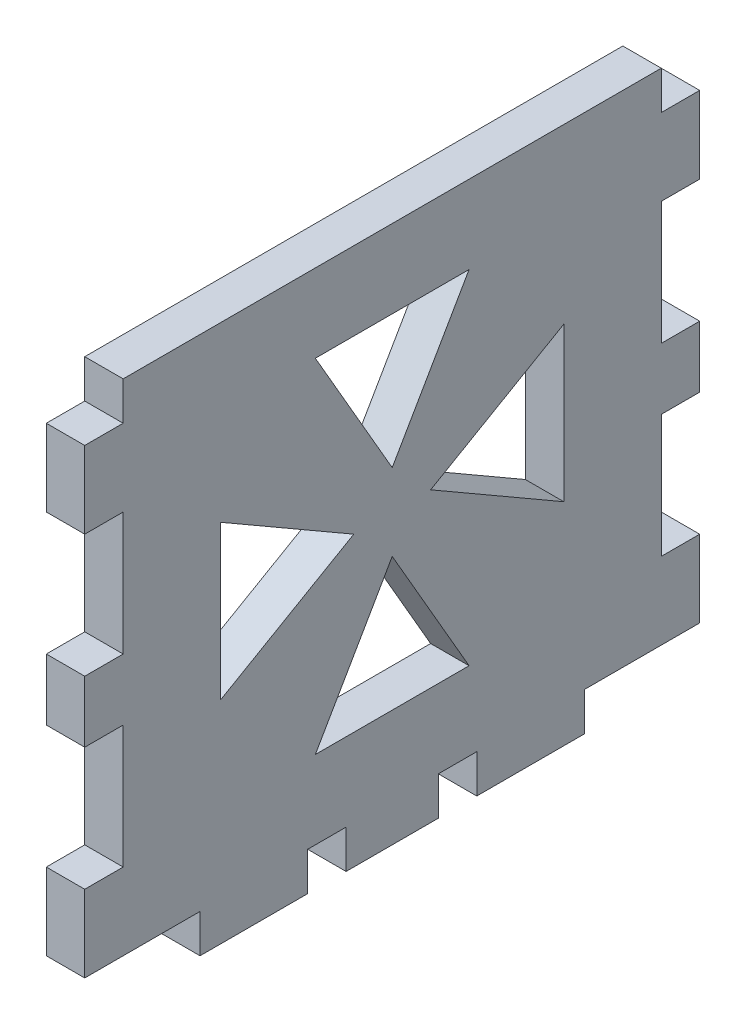
SolidWorks part; units mm, degrees
material "Pine"
ref_plane "Front Plane" through (0, 0, 0) normal (0, 0, 1) x (1, 0, 0)
ref_plane "Top Plane" through (0, 0, 0) normal (0, 1, 0) x (1, 0, 0)
ref_plane "Right Plane" through (0, 0, 0) normal (1, 0, 0) x (0, 0, -1)
sketch "Sketch1" plane through (0, 0, 0) normal (1, 0, 0) x (0, 0, -1)
  line L0 (50.8, 0) -> (50.8, 88.9) construction
  line L1 (0, 0) -> (101.6, 0)
  line L2 (0, 0) -> (0, 88.9)
  line L3 (0, 88.9) -> (101.6, 88.9)
  line L4 (101.6, 0) -> (101.6, 88.9)
  line L5 (0, 0) -> (6.35, 0)
  line L6 (0, 0) -> (0, 6.35)
  line L7 (0, 6.35) -> (6.35, 6.35)
  line L8 (6.35, 0) -> (6.35, 6.35)
  line L9 (101.6, 0) -> (95.25, 0)
  line L10 (101.6, 0) -> (101.6, 6.35)
  line L11 (101.6, 6.35) -> (95.25, 6.35)
  line L12 (95.25, 0) -> (95.25, 6.35)
  line L13 (0, 88.9) -> (6.35, 88.9)
  line L14 (0, 88.9) -> (0, 82.55)
  line L15 (0, 82.55) -> (6.35, 82.55)
  line L16 (6.35, 88.9) -> (6.35, 82.55)
  line L17 (101.6, 88.9) -> (95.25, 88.9)
  line L18 (101.6, 88.9) -> (101.6, 82.55)
  line L19 (101.6, 82.55) -> (95.25, 82.55)
  line L20 (95.25, 88.9) -> (95.25, 82.55)
  line L21 (101.6, 69.85) -> (95.25, 69.85)
  line L22 (101.6, 69.85) -> (101.6, 49.53)
  line L23 (101.6, 49.53) -> (95.25, 49.53)
  line L24 (95.25, 69.85) -> (95.25, 49.53)
  line L25 (101.6, 19.05) -> (95.25, 19.05)
  line L26 (101.6, 19.05) -> (101.6, 39.37)
  line L27 (101.6, 39.37) -> (95.25, 39.37)
  line L28 (95.25, 19.05) -> (95.25, 39.37)
  line L29 (0, 39.37) -> (6.35, 39.37)
  line L30 (6.35, 19.05) -> (6.35, 39.37)
  line L31 (0, 19.05) -> (6.35, 19.05)
  line L32 (0, 19.05) -> (0, 39.37)
  line L33 (0, 49.53) -> (6.35, 49.53)
  line L34 (6.35, 69.85) -> (6.35, 49.53)
  line L35 (0, 69.85) -> (6.35, 69.85)
  line L36 (0, 69.85) -> (0, 49.53)
  line L37 (6.35, 6.35) -> (95.25, 6.35)
  line L38 (6.35, 6.35) -> (95.25, 6.35)
  line L40 (19.05, 0) -> (36.83, 0)
  line L41 (19.05, 0) -> (19.05, 6.35)
  line L42 (19.05, 6.35) -> (36.83, 6.35)
  line L43 (36.83, 0) -> (36.83, 6.35)
  line L44 (64.77, 0) -> (82.55, 0)
  line L45 (64.77, 0) -> (64.77, 6.35)
  line L46 (64.77, 6.35) -> (82.55, 6.35)
  line L47 (82.55, 0) -> (82.55, 6.35)
  line L48 (43.18, 0) -> (58.42, 0)
  line L49 (43.18, 0) -> (43.18, 6.35)
  line L50 (43.18, 6.35) -> (58.42, 6.35)
  line L51 (58.42, 0) -> (58.42, 6.35)
  point P25 (98.425, 69.85)
  dimension "D1" = 101.6
  dimension "D2" = 88.9
  dimension "D3" = 6.35
  dimension "D4" = 6.35
  dimension "D5" = 6.35
  dimension "D6" = 6.35
  dimension "D7" = 6.35
  dimension "D8" = 6.35
  dimension "D9" = 6.35
  dimension "D10" = 6.35
  dimension "D11" = 12.7
  dimension "D12" = 12.7
  dimension "D13" = 20.32
  dimension "D14" = 20.32
  dimension "D15" = 12.7
  dimension "D16" = 12.7
  dimension "D17" = 17.78
  dimension "D18" = 17.78
  dimension "D19" = 6.35
  dimension "D20" = 6.35
extrude "Boss-Extrude1" add sketch "Sketch1" along normal blind 6.35 contours L1 L0 L3 L16 L15 L2 L35 L34 L33 L29 L30 L31 L7 L8 | L0 L1 L12 L11 L4 L25 L28 L27 L23 L24 L21 L19 L20 L3 | L41 L40 L43 L42 | L49 L48 L51 L50 | L45 L44 L47 L46 region at (0, 47.4409, -50.8)
sketch "Sketch2" plane through (6.35, 0, 0) normal (1, 0, 0) x (0, 0, -1)
  line L0 (50.8, 88.9) -> (50.8, 0) construction
  line L1 (44.45, 47.625) -> (22.453, 60.325)
  line L2 (22.453, 60.325) -> (22.453, 34.925)
  line L3 (22.453, 34.925) -> (44.45, 47.625)
  line L4 (6.35, 88.9) -> (95.25, 88.9) construction
  line L6 (50.8, 53.975) -> (63.5, 75.972)
  line L7 (101.6, 39.37) -> (101.6, 49.53) construction
  line L8 (101.6, 47.625) -> (0, 47.625) construction
  line L9 (0, 39.37) -> (0, 49.53) construction
  line L10 (63.5, 75.972) -> (38.1, 75.972)
  line L11 (38.1, 75.972) -> (50.8, 53.975)
  line L12 (57.15, 47.625) -> (79.147, 34.925)
  line L13 (79.147, 34.925) -> (79.147, 60.325)
  line L14 (79.147, 60.325) -> (57.15, 47.625)
  line L15 (50.8, 41.275) -> (38.1, 19.278)
  line L16 (38.1, 19.278) -> (63.5, 19.278)
  line L17 (63.5, 19.278) -> (50.8, 41.275)
  line L18 (43.18, 0) -> (58.42, 0) construction
  circle A0 centre (29.7853, 47.625) radius 7.3323 construction
  point P10 (50.8, 0)
  point P15 (50.8, 6.35)
  point P20 (50.8, 47.625)
  point P29 (50.8, 47.625)
  dimension "D1" = 6.35
  dimension "=" = 41.275
  dimension "D2" = 4
  dimension "D3" = 25.4
extrude "Cut-Extrude1" cut sketch "Sketch2" against normal up to surface (6.35 mm away) up to face at (0, 35.2778, -50.8)
